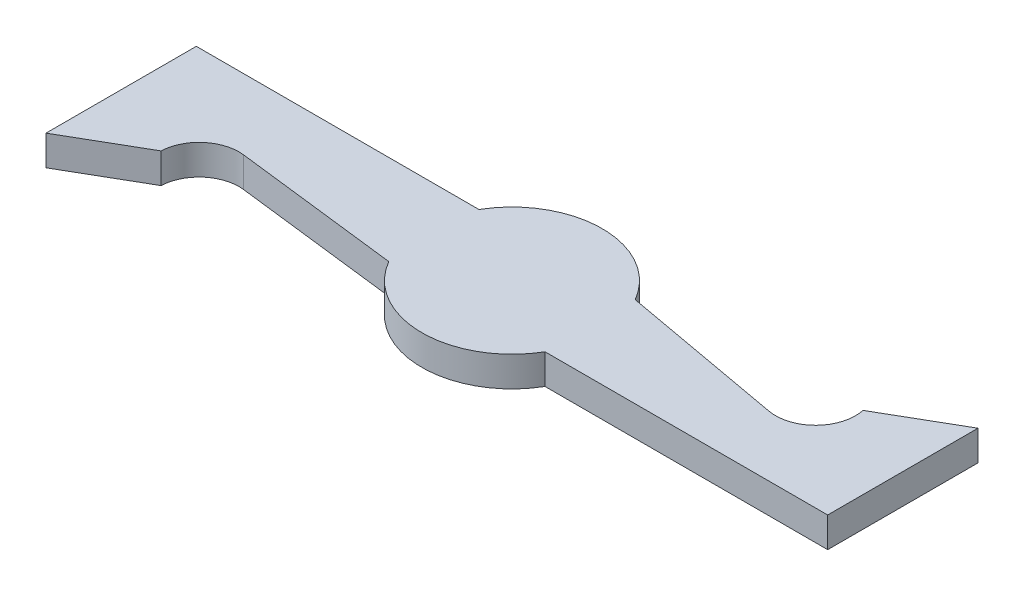
SolidWorks part; units mm, degrees
material "AR 500"
ref_plane "Front Plane" through (0, 0, 0) normal (0, 0, 1) x (1, 0, 0)
ref_plane "Top Plane" through (0, 0, 0) normal (0, 1, 0) x (1, 0, 0)
ref_plane "Right Plane" through (0, 0, 0) normal (1, 0, 0) x (0, 0, -1)
sketch "Sketch1" plane through (0, 0, 0) normal (0, 1, 0) x (1, 0, 0)
  line L0 (-33.0032, 19.05) -> (-152.4, 19.05)
  line L1 (-152.4, 50.8) -> (152.4, 50.8)
  line L2 (-152.4, 50.8) -> (-152.4, -50.8)
  line L3 (-152.4, -50.8) -> (152.4, -50.8)
  line L4 (152.4, 50.8) -> (152.4, -50.8)
  line L5 (-152.4, 50.8) -> (152.4, -50.8) construction
  line L6 (-152.4, -50.8) -> (152.4, 50.8) construction
  line L7 (-33.0032, 19.05) -> (32.9879, 19.05) construction
  line L8 (-33.0032, 19.05) -> (-33.0032, -19.05) construction
  line L9 (-33.0032, -19.05) -> (32.9879, -19.05) construction
  line L10 (32.9879, 19.05) -> (32.9879, -19.05) construction
  line L11 (-33.0032, 19.05) -> (32.9879, -19.05) construction
  line L12 (-33.0032, -19.05) -> (32.9879, 19.05) construction
  line L13 (-152.4, 19.05) -> (-152.4, -44.45)
  line L14 (-152.4, -44.45) -> (-121.6041, -26.67)
  line L15 (-102.747, -10.6692) -> (-33.0032, -19.05)
  line L16 (32.9879, -19.05) -> (152.4, -19.05)
  line L17 (152.4, -19.05) -> (152.4, 44.45)
  line L18 (152.4, 44.45) -> (121.6041, 26.67)
  line L19 (102.1149, 6.5271) -> (32.9879, 19.05)
  circle A0 centre (-0.0076, 0) radius 38.1
  arc A1 (-121.6041, -26.67) -> (-102.747, -10.6692) centre (-104.7587, -27.4105) cw
  arc A2 (121.6041, 26.67) -> (102.1149, 6.5271) centre (105.1206, 23.1188) cw
  point P1 (0, 0)
  dimension "D3" = 76.2
  dimension "D12" = 16.8617
  dimension "D13" = 16.8617
  dimension "D1" = 101.6
  dimension "D2" = 304.8
  dimension "D4" = 0.0076
  dimension "D5" = 38.1
  dimension "D6" = 63.5
  dimension "D7" = 60
  dimension "D8" = 35.56
  dimension "D9" = 63.5
  dimension "D10" = 60
  dimension "D11" = 35.56
extrude "Boss-Extrude1" add sketch "Sketch1" along normal blind 12.7 contours L14 A1 L15 A0 L0 L2 | A0 | L18 A2 L19 A0 L16 L4 region at (-100.1502, 0, 1.772) region at (-0.0076, 0, 0) region at (100.5992, 0, -1.2081)
